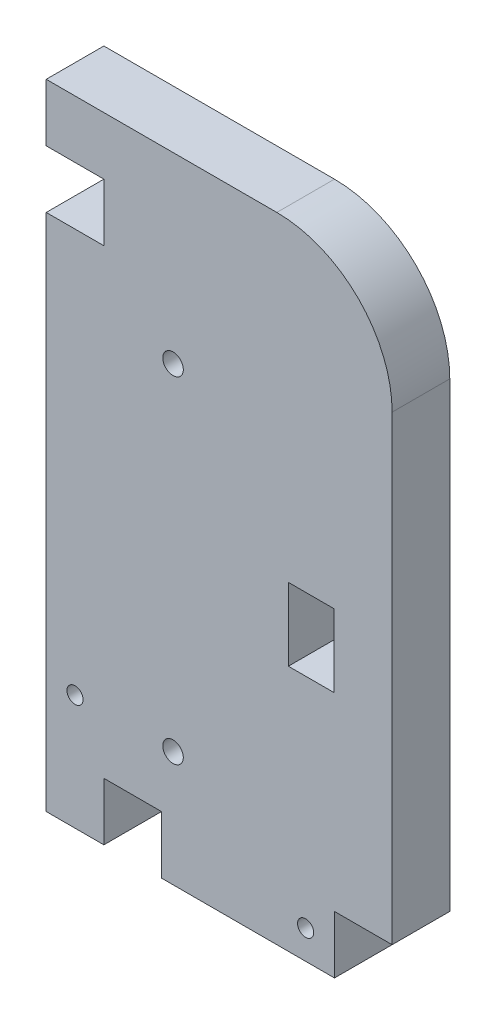
SolidWorks part; units mm, degrees
ref_plane "Front Plane" through (0, 0, 0) normal (0, 0, 1) x (1, 0, 0)
ref_plane "Top Plane" through (0, 0, 0) normal (0, 1, 0) x (1, 0, 0)
ref_plane "Right Plane" through (0, 0, 0) normal (1, 0, 0) x (0, 0, -1)
sketch "Sketch1" plane through (0, 0, 0) normal (0, 0, 1) x (1, 0, 0)
  line L0 (-16.1345, 9.3173) -> (-16.1345, -47.8327)
  line L1 (-16.1345, 22.0173) -> (9.2655, 22.0173)
  line L2 (-16.1345, 22.0173) -> (-16.1345, 15.6673)
  line L3 (-3.4345, -47.8327) -> (15.6155, -47.8327)
  line L4 (21.9655, 9.3173) -> (21.9655, -41.4827)
  line L5 (-16.1345, 15.6673) -> (-9.7845, 15.6673)
  line L7 (-16.1345, 9.3173) -> (-9.7845, 9.3173)
  line L8 (-9.7845, 15.6673) -> (-9.7845, 9.3173)
  line L9 (10.5355, -12.6327) -> (15.5355, -12.6327)
  line L10 (10.5355, -12.6327) -> (10.5355, -20.6327)
  line L11 (10.5355, -20.6327) -> (15.5355, -20.6327)
  line L12 (15.5355, -12.6327) -> (15.5355, -20.6327)
  line L13 (-9.7845, -47.8327) -> (-9.7845, -41.4827)
  line L14 (-9.7845, -41.4827) -> (-3.4345, -41.4827)
  line L15 (-16.1345, -47.8327) -> (-9.7845, -47.8327)
  line L16 (-3.4345, -47.8327) -> (-3.4345, -41.4827)
  line L19 (21.9655, -41.4827) -> (15.6155, -41.4827)
  line L20 (15.6155, -47.8327) -> (15.6155, -41.4827)
  circle A0 centre (-2.1645, -35.1327) radius 1.1303
  circle A1 centre (-2.1645, 1.8673) radius 1.1303
  circle A2 centre (12.4405, -44.6577) radius 0.889
  circle A3 centre (-12.9595, -35.1327) radius 0.889
  arc A4 (9.2655, 22.0173) -> (21.9655, 9.3173) centre (9.2655, 9.3173) cw
  dimension "D5" = 2.2606
  dimension "D6" = 2.2606
  dimension "D7" = 37
  dimension "D8" = 12.7
  dimension "D10" = 7.62
  dimension "D11" = 0
  dimension "D12" = 14.5
  dimension "D21" = 3.175
  dimension "D22" = 3.175
  dimension "D23" = 1.778
  dimension "D24" = 12.7
  dimension "D9" = 12.7
  dimension "D1" = 6.35
  dimension "D2" = 6.35
  dimension "D3" = 6.35
  dimension "D4" = 57.15
  dimension "D13" = 8
  dimension "D14" = 12.7
  dimension "D15" = 5
  dimension "D16" = 6.35
  dimension "D17" = 6.35
  dimension "D18" = 6.35
  dimension "D19" = 6.35
  dimension "D20" = 6.35
extrude "Boss-Extrude1" add sketch "Sketch1" along normal blind 6.35
